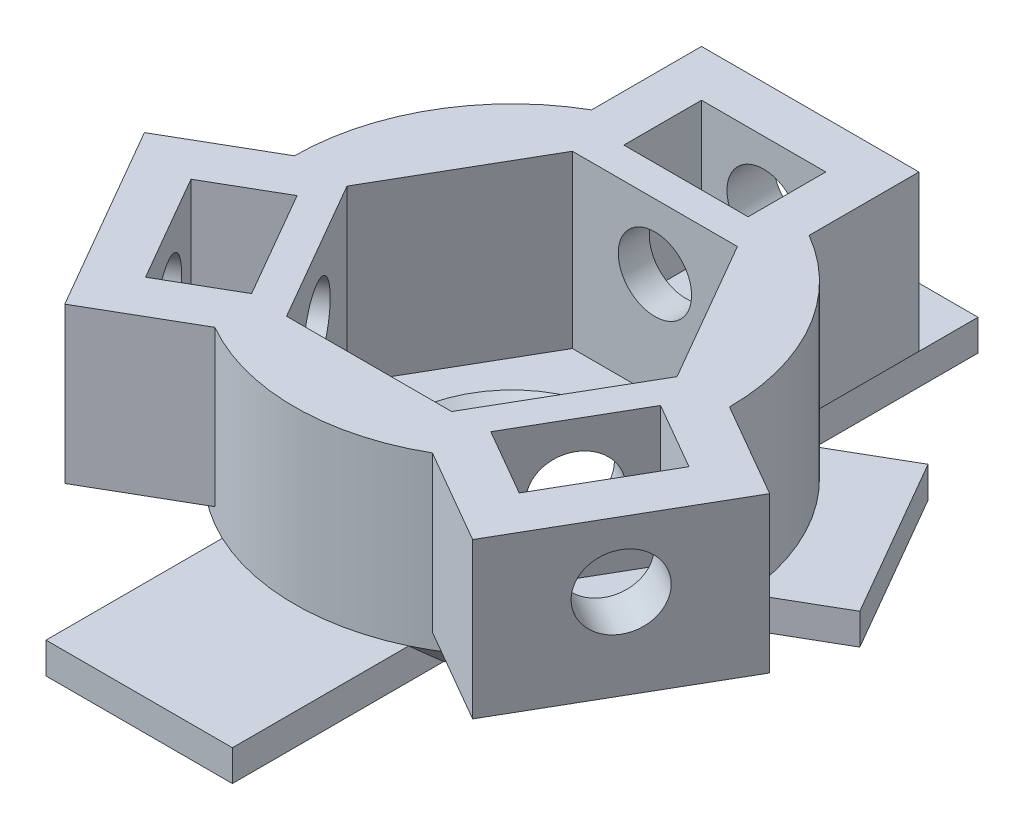
SolidWorks part; units mm, degrees
other "Markup1"
sketch "Sketch10" plane through (-5.0319, 3.25, -6) normal (-0.1458, 0.9881, -0.0488) x (0.3696, 0.1002, 0.9238)
material "Nickel"
ref_plane "Front Plane" through (0, 0, 0) normal (0, 0, 1) x (1, 0, 0)
ref_plane "Top Plane" through (0, 0, 0) normal (0, 1, 0) x (1, 0, 0)
ref_plane "Right Plane" through (0, 0, 0) normal (1, 0, 0) x (0, 0, -1)
sketch "Sketch1" plane through (0, 0, 0) normal (0, 1, 0) x (1, 0, 0)
  circle A0 centre (0, 0) radius 3.5
  dimension "D1" = 7
extrude "Boss-Extrude1" add sketch "Sketch1" along normal blind 3.25
sketch "Sketch2" plane through (0, 3.25, 0) normal (0, 1, 0) x (1, 0, 0)
  line L1 (1.3279, -2.3) -> (2.6558, 0)
  line L2 (2.6558, 0) -> (1.3279, 2.3)
  line L3 (1.3279, 2.3) -> (-1.3279, 2.3)
  line L4 (-1.3279, 2.3) -> (-2.6558, 0)
  line L5 (-2.6558, 0) -> (-1.3279, -2.3)
  line L6 (-1.3279, -2.3) -> (1.3279, -2.3)
  circle A0 centre (0, 0) radius 2.3 construction
  dimension "D1" = 4.6
extrude "Cut-Extrude1" cut sketch "Sketch2" against normal blind 2.75
sketch "Sketch3" plane through (0, 0.5, 0) normal (0, 1, 0) x (1, 0, 0)
  circle A0 centre (0, 0) radius 1.5
  dimension "D1" = 3
extrude "Cut-Extrude2" cut sketch "Sketch3" against normal through all
sketch "Sketch4" plane through (0, 0, 0) normal (0, -1, 0) x (1, 0, 0)
  line L0 (-1.5, 4.5) -> (-1.5, 3.1623)
  line L1 (-1.5, 4.5) -> (1.5, 4.5) construction
  line L2 (1.5, 4.5) -> (1.5, 3.1623)
  line L3 (4.6471, -0.951) -> (3.4886, -0.2821)
  line L4 (4.6471, -0.951) -> (3.1471, -3.549)
  line L5 (3.1471, -3.549) -> (1.9886, -2.8802)
  line L6 (-3.1471, -3.549) -> (-1.9886, -2.8802)
  line L7 (-3.1471, -3.549) -> (-4.6471, -0.951)
  line L8 (-4.6471, -0.951) -> (-3.4886, -0.2821)
  line L9 (1.5, -4.5) -> (1.5, -3.1623)
  line L10 (-1.5, 4.5) -> (1.5, 4.5) construction
  line L11 (-1.5, 4.5) -> (-1.5, 6)
  line L12 (-1.5, 6) -> (1.5, 6)
  line L13 (1.5, 4.5) -> (1.5, 6)
  line L14 (-1.5, -4.5) -> (-1.5, -3.1623)
  line L15 (-1.5, -4.5) -> (-1.5, -6)
  line L16 (1.5, -4.5) -> (1.5, -6)
  line L17 (1.5, -6) -> (-1.5, -6)
  arc A0 (1.5, 3.1623) -> (-1.5, 3.1623) centre (0, 0) ccw
  circle A1 centre (0, 0) radius 3.5 construction
  arc A2 (1.9886, -2.8802) -> (3.4886, -0.2821) centre (0, 0) ccw
  arc A3 (-3.4886, -0.2821) -> (-1.9886, -2.8802) centre (0, 0) ccw
  arc A4 (-1.5, -3.1623) -> (1.5, -3.1623) centre (0, 0) ccw
  point P1 (0, 4.5)
  point P11 (3.8971, -2.25)
  point P16 (-3.8971, -2.25)
  point P21 (0, 0)
  dimension "D1" = 4.5
  dimension "D2" = 3
  dimension "D4" = 1.5
  dimension "D3" = 3
  dimension "D5" = 2
extrude "Boss-Extrude6" add sketch "Sketch4" against normal blind 0.5
ref_plane "Plane1" through (0, 0, -2.8) normal (0, 0, 1) x (1, 0, 0)
sketch "Sketch6" plane through (0, 0, -2.8) normal (0, 0, 1) x (1, 0, 0)
  line L1 (1.75, 3.25) -> (-1.75, 3.25)
  line L2 (1.75, 3.25) -> (1.75, 0.75)
  line L3 (1.75, 0.75) -> (-1.75, 0.75)
  line L4 (-1.75, 3.25) -> (-1.75, 0.75)
  line L5 (1.75, 3.25) -> (-1.75, 0.75) construction
  line L6 (1.75, 0.75) -> (-1.75, 3.25) construction
  line L7 (3.5, 3.25) -> (-3.5, 3.25) construction
  point P0 (0, 2)
  dimension "D2" = 2.5
  dimension "D3" = 3.5
extrude "Boss-Extrude4" add sketch "Sketch6" against normal blind 2 and the other way blind 0.5
sketch "Sketch7" plane through (0, 3.25, 0) normal (0, 1, 0) x (1, 0, 0)
  line L0 (1.3279, 2.3) -> (-1.3279, 2.3) construction
  line L1 (-1, 4.05) -> (1, 4.05)
  line L2 (-1, 4.05) -> (-1, 2.8)
  line L3 (-1, 2.8) -> (1, 2.8)
  line L4 (1, 4.05) -> (1, 2.8)
  line L5 (-1, 4.05) -> (1, 2.8) construction
  line L6 (-1, 2.8) -> (1, 4.05) construction
  point P0 (0, 3.425)
  dimension "D1" = 1.25
  dimension "D2" = 0.5
  dimension "D3" = 2
extrude "Cut-Extrude3" cut sketch "Sketch7" against normal blind 2.23
sketch "Sketch8" plane through (0, 0, -4.8) normal (0, 0, -1) x (-1, 0, 0)
  line L0 (-1.75, 3.25) -> (1.75, 3.25) construction
  circle A0 centre (0, 2.2) radius 0.59
  dimension "D1" = 1.18
  dimension "D2" = 1.05
extrude "Cut-Extrude4" cut sketch "Sketch8" against normal blind 4
chamfer "Chamfer2" [suppressed] distance 0.25 angle 45
chamfer "Chamfer3" distance 0.5 angle 45 3 edges at (-3.0311, 0, 1.75) (1.75, 0, -3.0311) (3.0311, 0, 1.75)
pattern_circular "CirPattern1" count 3 over 360 about axis through (0, 0, 0) along (0, 1, 0) of "Boss-Extrude4", "Chamfer2", "Cut-Extrude4", "Cut-Extrude3"
chamfer "Chamfer4" distance 0.25 angle 45 2 edges at (0, 0.5, 1.5) (0, 0, 1.5)
sketch "Sketch9" [suppressed] plane through (0, 3.25, 0) normal (0, 1, 0) x (1, 0, 0)
  line L0 (-1.75, 4.1458) -> (-1.75, 3.0311)
  line L1 (-1.75, 3.0311) -> (-1.75, 4.3) construction
  line L2 (1.75, 4.1458) -> (1.75, 3.0311)
  line L3 (1.75, 3.0311) -> (1.75, 4.3) construction
  line L4 (-4.4654, -0.5573) -> (-3.5, 0)
  line L5 (-3.5, 0) -> (-4.5989, -0.6345) construction
  line L6 (-2.7154, -3.5884) -> (-1.75, -3.0311)
  line L7 (-1.75, -3.0311) -> (-2.8489, -3.6655) construction
  line L8 (1.75, -3.0311) -> (2.7154, -3.5884)
  line L9 (1.75, -3.0311) -> (2.8489, -3.6655) construction
  line L10 (4.4654, -0.5573) -> (3.5, 0)
  line L11 (3.5, 0) -> (4.5989, -0.6345) construction
  arc A0 (-1.75, 3.0311) -> (-3.5, 0) centre (0, 0) ccw
  arc A1 (-1.75, 4.1458) -> (-4.4654, -0.5573) centre (0, 0) ccw
  arc A2 (-2.7154, -3.5884) -> (2.7154, -3.5884) centre (0, 0) ccw
  arc A3 (-1.75, -3.0311) -> (1.75, -3.0311) centre (0, 0) ccw
  arc A4 (4.4654, -0.5573) -> (1.75, 4.1458) centre (0, 0) ccw
  arc A5 (3.5, 0) -> (1.75, 3.0311) centre (0, 0) ccw
  dimension "D2" = 9
extrude "Boss-Extrude5" [suppressed] add sketch "Sketch9" against normal blind 1
